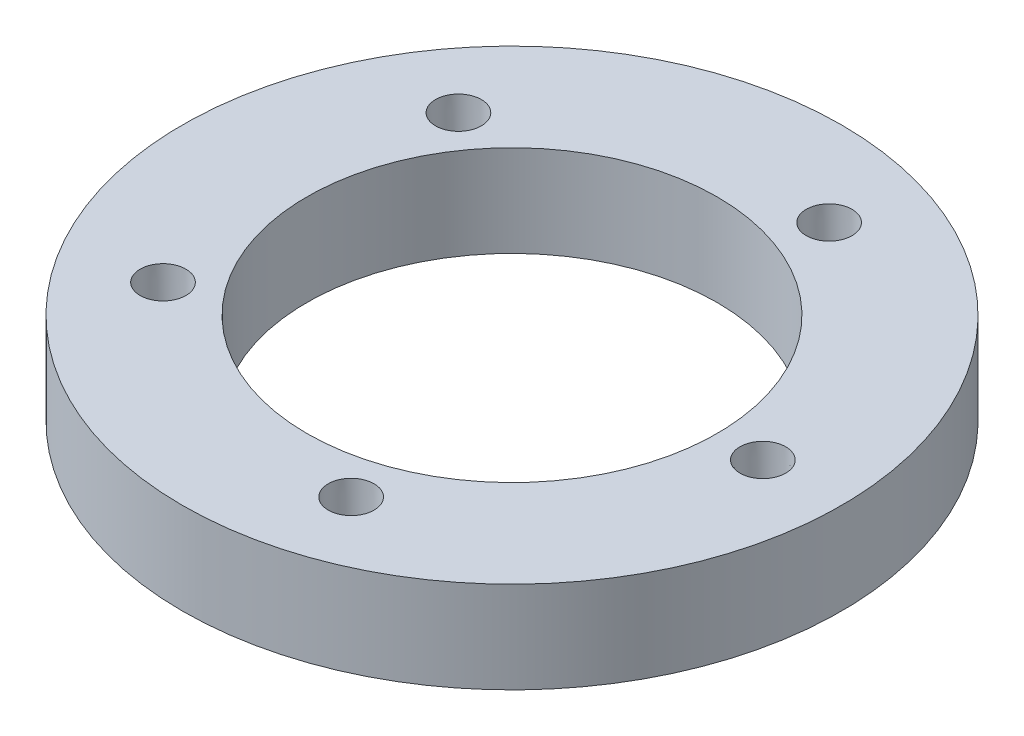
SolidWorks part; units mm, degrees
ref_plane "Front Plane" through (0, 0, 0) normal (0, 0, 1) x (1, 0, 0)
ref_plane "Top Plane" through (0, 0, 0) normal (0, 1, 0) x (1, 0, 0)
ref_plane "Right Plane" through (0, 0, 0) normal (1, 0, 0) x (0, 0, -1)
sketch "Sketch1" plane through (0, 0, 0) normal (0, 1, 0) x (1, 0, 0)
  circle A0 centre (0, 0) radius 11.2
  circle A1 centre (0, 0) radius 16.2
  dimension "D1" = 22.4
  dimension "D2" = 5
extrude "Boss-Extrude2" add sketch "Sketch1" along normal blind 5
sketch "Sketch2" plane through (0, 5, 0) normal (0, 1, 0) x (1, 0, 0)
  line L0 (-11.2, 0) -> (-16.2, 0) construction
  line L1 (-12.5, 0.9943) -> (-12.5, -1.1473) construction
  line L2 (0.0123, 0.0374) -> (12.4508, 0.046) construction
  circle A0 centre (0, 0) radius 11.2 construction
  circle A1 centre (0, 0) radius 16.2 construction
  arc A2 (-11.7329, 7.0732) -> (-11.8029, -6.9556) centre (0, 0) ccw
  circle A3 centre (13.7, 0) radius 1.25
  circle A4 centre (4.2064, -12.9919) radius 1.25
  circle A5 centre (-11.0833, -7.9777) radius 1.25
  circle A6 centre (-11.0393, 8.1132) radius 1.25
  circle A7 centre (4.2776, 13.0437) radius 1.25
  arc A8 (3.0664, 13.3524) -> (-10.2539, 9.0856) centre (0, 0) ccw
  arc A9 (13.643, 1.2487) -> (5.4365, 12.5752) centre (0, 0) ccw
  arc A10 (5.3915, -12.5945) -> (13.643, -1.2487) centre (0, 0) ccw
  arc A11 (-10.3425, -8.9846) -> (3.0132, -13.3645) centre (0, 0) ccw
  dimension "D1" = 2.5
  dimension "D3" = 2.5
  dimension "D2" = 5
extrude "Cut-Extrude1" cut sketch "Sketch2" against normal blind 5 draft 2 contours A6 | A5 | A4 | A3 | A7 region at (-11.0393, 5, -8.1132) region at (-11.0833, 5, 7.9777) region at (4.2776, 5, -13.0437) region at (4.2064, 5, 12.9919) region at (13.7, 5, 0)
sketch "Sketch3" plane through (0, 5, 0) normal (0, 1, 0) x (1, 0, 0)
  circle A0 centre (0, 0) radius 16
  circle A1 centre (0, 0) radius 18
  dimension "D1" = 2
extrude "Boss-Extrude4" add sketch "Sketch3" against normal up to surface (5 mm away) up to face at (4.2776, 0, -11.9683)
equation "\"outer-diameter\"= 20"
equation "\"screw-diameter\"= 2"
equation "\"bearing-thickness\"= 5"
